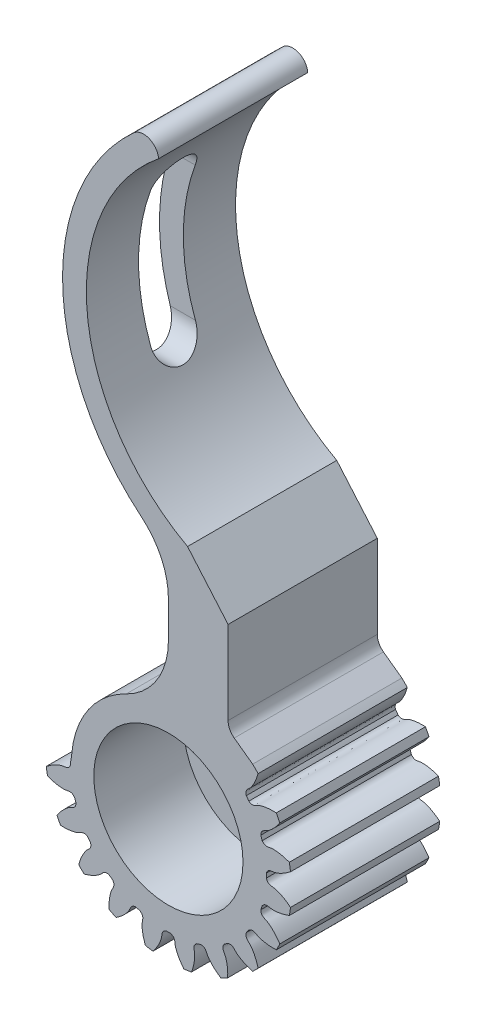
SolidWorks part; units mm, degrees
material "聚脂树脂"
ref_plane "前视基准面" through (0, 0, 0) normal (0, 0, 1) x (1, 0, 0)
ref_plane "上视基准面" through (0, 0, 0) normal (0, 1, 0) x (1, 0, 0)
ref_plane "右视基准面" through (0, 0, 0) normal (1, 0, 0) x (0, 0, -1)
other "Configuration Table"
sketch "草图1" plane through (0, 0, 0) normal (0, 0, 1) x (1, 0, 0)
  circle A0 centre (0, 0) radius 16.5
extrude "凸台-拉伸1" add sketch "草图1" along normal blind 20
ref_axis "基准轴1" through (0, 0, -1.5) along (0, 0, 1)
sketch "草图2" plane through (0, 0, 0) normal (0, 0, 1) x (1, 0, 0)
  line L0 (0, 0) -> (0, 16.5) construction
  circle A0 centre (0, 0) radius 16.5 construction
  arc A1 (0.29, 13.1218) -> (-0.29, 13.1218) centre (0, 0) ccw
  arc A2 (4.7717, 18.7474) -> (-4.7717, 18.7474) centre (0, 0) ccw
  spline S0 degree 3 poles (0.29, 13.1218) (0.9168, 13.3402) (0.8356, 13.7807) (0.9193, 14.205) (0.9283, 14.2463) (0.9395, 14.293) (0.9529, 14.3448) (0.969, 14.4018) (0.9878, 14.4638) (1.0095, 14.5309) (1.0345, 14.6028) (1.0629, 14.6795) (1.0948, 14.7608) (1.1305, 14.8467) (1.1702, 14.9371) (1.2141, 15.0317) (1.2623, 15.1305) (1.315, 15.2334) (1.3725, 15.3401) (1.4349, 15.4506) (1.5023, 15.5646) (1.575, 15.6821) (1.653, 15.8029) (1.7366, 15.9267) (1.826, 16.0534) (1.9211, 16.1829) (2.0223, 16.3149) (2.1296, 16.4493) (2.2432, 16.5859) (2.3632, 16.7244) (2.4897, 16.8646) (2.6229, 17.0065) (2.7628, 17.1496) (2.9095, 17.2939) (3.0632, 17.4391) (3.224, 17.585) (3.3918, 17.7313) (3.567, 17.8779) (3.7493, 18.0245) (3.9391, 18.1709) (4.1363, 18.3167) (4.4122, 18.5125) (4.6259, 18.6545) (4.7717, 18.7474) knots 0 0 0 0 0.165916 0.170906 0.176664 0.183189 0.190482 0.198542 0.207371 0.216967 0.22733 0.238462 0.250361 0.263027 0.276462 0.290664 0.305634 0.321371 0.337876 0.355149 0.37319 0.391998 0.411574 0.431917 0.453028 0.474907 0.497554 0.520968 0.54515 0.570099 0.595817 0.622302 0.649554 0.677575 0.706363 0.735918 0.766242 0.797333 0.829191 0.861818 0.895212 0.929373 1 1 1 1
  spline S1 degree 3 poles (-0.29, 13.1218) (-0.9168, 13.3402) (-0.8356, 13.7807) (-0.9193, 14.205) (-0.9283, 14.2463) (-0.9395, 14.293) (-0.9529, 14.3448) (-0.969, 14.4018) (-0.9878, 14.4638) (-1.0095, 14.5309) (-1.0345, 14.6028) (-1.0629, 14.6795) (-1.0948, 14.7608) (-1.1305, 14.8467) (-1.1702, 14.9371) (-1.2141, 15.0317) (-1.2623, 15.1305) (-1.315, 15.2334) (-1.3725, 15.3401) (-1.4349, 15.4506) (-1.5023, 15.5646) (-1.575, 15.6821) (-1.653, 15.8029) (-1.7366, 15.9267) (-1.826, 16.0534) (-1.9211, 16.1829) (-2.0223, 16.3149) (-2.1296, 16.4493) (-2.2432, 16.5859) (-2.3632, 16.7244) (-2.4897, 16.8646) (-2.6229, 17.0065) (-2.7628, 17.1496) (-2.9095, 17.2939) (-3.0632, 17.4391) (-3.224, 17.585) (-3.3918, 17.7313) (-3.567, 17.8779) (-3.7493, 18.0245) (-3.9391, 18.1709) (-4.1363, 18.3167) (-4.4122, 18.5125) (-4.6259, 18.6545) (-4.7717, 18.7474) knots 0 0 0 0 0.165916 0.170906 0.176664 0.183189 0.190482 0.198542 0.207371 0.216967 0.22733 0.238462 0.250361 0.263027 0.276462 0.290664 0.305634 0.321371 0.337876 0.355149 0.37319 0.391998 0.411574 0.431917 0.453028 0.474907 0.497554 0.520968 0.54515 0.570099 0.595817 0.622302 0.649554 0.677575 0.706363 0.735918 0.766242 0.797333 0.829191 0.861818 0.895212 0.929373 1 1 1 1
extrude "切除-拉伸1" cut sketch "草图2" along normal through all
pattern_circular "阵列(圆周)1" count 20 over 360 about axis through (0, 0, -1.5) along (0, 0, 1) of "切除-拉伸1"
sketch "草图3" plane through (0, 0, 0) normal (0, 0, 1) x (1, 0, 0)
  circle A0 centre (0, 0) radius 15 construction
  dimension "Dn" = 30
sketch "草图4" plane through (0, 0, 0) normal (0, 0, -1) x (-1, 0, 0)
  line L0 (0, 0) -> (67.6919, 0) construction
  line L1 (0, 13.125) -> (0, 76.7697) construction
  line L2 (-15, 0) -> (-15, 67.6903) construction
  line L6 (-7.9502, 14.4584) -> (-11.294, 12.029)
  line L7 (-8, 0) -> (-8, 30.72)
  line L8 (0, 30.72) -> (0, 0)
  line L9 (1.261, 80) -> (1.32, 76)
  line L10 (-8, 0) -> (0, 0)
  circle A2 centre (-15, 55.76) radius 26 construction
  arc A4 (-8, 30.72) -> (1.32, 76) centre (-15, 55.76) ccw
  arc A6 (0.29, 13.1218) -> (-0.29, 13.1218) centre (0, 0) ccw construction
  arc A7 (-2.0665, 16.3701) -> (-3.0932, 16.2075) centre (0, 0) ccw construction
  arc A8 (-3.7791, 12.5692) -> (-4.3306, 12.39) centre (0, 0) ccw construction
  arc A9 (-7.024, 14.9303) -> (-7.9502, 14.4584) centre (0, 0) ccw construction
  arc A10 (0, 13.125) -> (-0.29, 13.1218) centre (0, 0) ccw
  arc A11 (-2.0665, 16.3701) -> (-3.0932, 16.2075) centre (0, 0) ccw
  arc A12 (-3.7791, 12.5692) -> (-4.3306, 12.39) centre (0, 0) ccw
  arc A13 (-7.024, 14.9303) -> (-7.9502, 14.4584) centre (0, 0) ccw
  arc A14 (-7.4782, 10.7862) -> (-7.9474, 10.4453) centre (0, 0) ccw construction
  arc A15 (-7.4782, 10.7862) -> (-7.9474, 10.4453) centre (0, 0) ccw
  circle A16 centre (0, 0) radius 12.5
  circle A17 centre (-15, 55.76) radius 29.189 construction
  arc A18 (0, 30.72) -> (1.261, 80) centre (-15, 55.76) ccw
  spline S2 degree 3 poles (3856.7688, 1071.746) (-40.9447, -7.0022) (0.397, 7.533) (-0.9224, 14.2207) (-0.9359, 14.2793) (-0.9529, 14.3448) (-0.969, 14.4018) (-0.9951, 14.4881) (-1.0357, 14.6084) (-1.0961, 14.7664) (-1.1716, 14.9426) (-1.2638, 15.1361) (-1.3741, 15.3456) (-1.5041, 15.5702) (-1.6549, 15.8084) (-1.7965, 16.0133) (-1.9211, 16.1829) (-22.6396, 43.218) (-204.8238, -56.137) (3987.8439, 293.2807) knots -2.601051 -2.601051 -2.601051 -2.601051 0.165916 0.170906 0.183189 0.190482 0.198542 0.207371 0.22733 0.250361 0.276462 0.305634 0.337876 0.37319 0.411574 0.453028 0.474907 0.497554 14.365332 14.365332 14.365332 14.365332 only from (-0.29, 13.1218) to (-2.0665, 16.3701) construction
  spline S3 degree 3 poles (-3999.1929, -172.5161) (41.1045, 5.9931) (-2.7054, 7.0416) (-3.5171, 13.8097) (-3.5224, 13.8696) (-3.5265, 13.9372) (-3.5289, 13.9963) (-3.5307, 14.0865) (-3.5293, 14.2134) (-3.5206, 14.3824) (-3.5033, 14.5733) (-3.4754, 14.7858) (-3.4352, 15.0192) (-3.381, 15.2729) (-3.3111, 15.5461) (-3.2398, 15.7847) (-3.1737, 15.9845) (8.1764, 48.0988) (212.1463, 9.9046) (-3883.2936, -953.385) knots -2.108482 -2.108482 -2.108482 -2.108482 0.658484 0.663474 0.675757 0.68305 0.691111 0.699939 0.719899 0.742929 0.76903 0.798202 0.830445 0.865758 0.904142 0.945597 0.967475 0.990122 14.8579 14.8579 14.8579 14.8579 only from (-3.7791, 12.5692) to (-3.0932, 16.2075) construction
  spline S4 degree 3 poles (3336.8174, 2211.0982) (-36.7769, -19.3121) (-1.9503, 7.287) (-5.2717, 13.2396) (-5.3027, 13.2912) (-5.3391, 13.3482) (-5.3719, 13.3975) (-5.4235, 13.4715) (-5.4992, 13.5733) (-5.6055, 13.705) (-5.7318, 13.8492) (-5.8792, 14.0047) (-6.0489, 14.1699) (-6.2419, 14.3433) (-6.459, 14.5233) (-6.6569, 14.6744) (-6.8279, 14.7972) (-34.8866, 34.1067) (-177.4517, -116.6835) (3702.0362, 1511.238) knots -2.601051 -2.601051 -2.601051 -2.601051 0.165916 0.170906 0.183189 0.190482 0.198542 0.207371 0.22733 0.250361 0.276462 0.305634 0.337876 0.37319 0.411574 0.453028 0.474907 0.497554 14.365332 14.365332 14.365332 14.365332 only from (-4.3306, 12.39) to (-7.024, 14.9303) construction
  spline S5 degree 3 poles (-0.29, 13.1218) (-0.9168, 13.3402) (-0.8356, 13.7807) (-0.9224, 14.2207) (-0.9359, 14.2793) (-0.9529, 14.3448) (-0.969, 14.4018) (-0.9951, 14.4881) (-1.0357, 14.6084) (-1.0961, 14.7664) (-1.1716, 14.9426) (-1.2638, 15.1361) (-1.3741, 15.3456) (-1.5041, 15.5702) (-1.6549, 15.8084) (-1.828, 16.0589) (-1.969, 16.2466) (-2.0515, 16.3512) (-2.0665, 16.3701) knots 0 0 0 0 0.165916 0.170906 0.183189 0.190482 0.198542 0.207371 0.22733 0.250361 0.276462 0.305634 0.337876 0.37319 0.411574 0.453028 0.497554 0.507432 0.507432 0.507432 0.507432
  spline S6 degree 3 poles (-3.7791, 12.5692) (-3.2504, 12.9706) (-3.4637, 13.3644) (-3.5171, 13.8097) (-3.5224, 13.8696) (-3.5265, 13.9372) (-3.5289, 13.9963) (-3.5307, 14.0865) (-3.5293, 14.2134) (-3.5206, 14.3824) (-3.5033, 14.5733) (-3.4754, 14.7858) (-3.4352, 15.0192) (-3.381, 15.2729) (-3.3111, 15.5461) (-3.224, 15.8378) (-3.1479, 16.0599) (-3.1017, 16.1848) (-3.0932, 16.2075) knots 0.492568 0.492568 0.492568 0.492568 0.658484 0.663474 0.675757 0.68305 0.691111 0.699939 0.719899 0.742929 0.76903 0.798202 0.830445 0.865758 0.904142 0.945597 0.990122 1 1 1 1
  spline S7 degree 3 poles (-4.3306, 12.39) (-4.9943, 12.404) (-5.0532, 12.848) (-5.2717, 13.2396) (-5.3027, 13.2912) (-5.3391, 13.3482) (-5.3719, 13.3975) (-5.4235, 13.4715) (-5.4992, 13.5733) (-5.6055, 13.705) (-5.7318, 13.8492) (-5.8792, 14.0047) (-6.0489, 14.1699) (-6.2419, 14.3433) (-6.459, 14.5233) (-6.701, 14.7081) (-6.8931, 14.843) (-7.0039, 14.9169) (-7.024, 14.9303) knots 0 0 0 0 0.165916 0.170906 0.183189 0.190482 0.198542 0.207371 0.22733 0.250361 0.276462 0.305634 0.337876 0.37319 0.411574 0.453028 0.497554 0.507432 0.507432 0.507432 0.507432
  spline S8 degree 3 poles (-3750.148, -1399.8911) (37.2407, 18.4018) (-4.7489, 5.861) (-7.6124, 12.047) (-7.636, 12.1023) (-7.6607, 12.1653) (-7.6812, 12.2208) (-7.7108, 12.3061) (-7.7487, 12.4272) (-7.7927, 12.5905) (-7.8352, 12.7775) (-7.8743, 12.9882) (-7.9082, 13.2226) (-7.9351, 13.4806) (-7.9531, 13.762) (-7.959, 14.011) (-7.9578, 14.2215) (-7.0871, 48.2713) (198.7024, 74.9766) (-3398.6195, -2106.7268) knots -2.108482 -2.108482 -2.108482 -2.108482 0.658484 0.663474 0.675757 0.68305 0.691111 0.699939 0.719899 0.742929 0.76903 0.798202 0.830445 0.865758 0.904142 0.945597 0.967475 0.990122 14.8579 14.8579 14.8579 14.8579 only from (-7.4782, 10.7862) to (-7.9502, 14.4584) construction
  spline S9 degree 3 poles (2490.235, 3134.0126) (-29.0091, -29.7316) (-4.1066, 6.3277) (-9.105, 10.9626) (-9.1503, 11.0021) (-9.2026, 11.0451) (-9.2491, 11.0817) (-9.321, 11.1362) (-9.4245, 11.2097) (-9.5662, 11.302) (-9.7309, 11.4002) (-9.9192, 11.5025) (-10.1316, 11.6072) (-10.3687, 11.7125) (-10.6308, 11.8165) (-10.8658, 11.8991) (-11.0663, 11.963) (-43.7187, 21.6569) (-132.7094, -165.8082) (3053.8474, 2581.2649) knots -2.601051 -2.601051 -2.601051 -2.601051 0.165916 0.170906 0.183189 0.190482 0.198542 0.207371 0.22733 0.250361 0.276462 0.305634 0.337876 0.37319 0.411574 0.453028 0.474907 0.497554 14.365332 14.365332 14.365332 14.365332 only from (-7.9474, 10.4453) to (-11.294, 12.029) construction
  spline S10 degree 3 poles (-7.4782, 10.7862) (-7.0995, 11.3313) (-7.424, 11.64) (-7.6124, 12.047) (-7.636, 12.1023) (-7.6607, 12.1653) (-7.6812, 12.2208) (-7.7108, 12.3061) (-7.7487, 12.4272) (-7.7927, 12.5905) (-7.8352, 12.7775) (-7.8743, 12.9882) (-7.9082, 13.2226) (-7.9351, 13.4806) (-7.9531, 13.762) (-7.9603, 14.0664) (-7.9566, 14.3011) (-7.9513, 14.4342) (-7.9502, 14.4584) knots 0.492568 0.492568 0.492568 0.492568 0.658484 0.663474 0.675757 0.68305 0.691111 0.699939 0.719899 0.742929 0.76903 0.798202 0.830445 0.865758 0.904142 0.945597 0.990122 1 1 1 1
  spline S11 degree 3 poles (-7.9474, 10.4453) (-8.5829, 10.2536) (-8.7761, 10.6576) (-9.105, 10.9626) (-9.1503, 11.0021) (-9.2026, 11.0451) (-9.2491, 11.0817) (-9.321, 11.1362) (-9.4245, 11.2097) (-9.5662, 11.302) (-9.7309, 11.4002) (-9.9192, 11.5025) (-10.1316, 11.6072) (-10.3687, 11.7125) (-10.6308, 11.8165) (-10.9181, 11.9175) (-11.1425, 11.9864) (-11.2707, 12.0225) (-11.294, 12.029) knots 0 0 0 0 0.165916 0.170906 0.183189 0.190482 0.198542 0.207371 0.22733 0.250361 0.276462 0.305634 0.337876 0.37319 0.411574 0.453028 0.497554 0.507432 0.507432 0.507432 0.507432
  dimension "D4" = 52
  dimension "D5" = 80
  dimension "D3" = 25
  dimension "D1" = 15
  dimension "D2" = 30.72
  dimension "D6" = 76
  dimension "D8" = 8
  dimension "D9" = 30.72
extrude "凸台-拉伸2" add sketch "草图4" against normal blind 20 contours S7 A12 S6 A11 S5 A10 L8 A18 L9 A4 L7 L6 A13 | S11 L7 L6 | L6 S11 A15 S10 region at (7.2884, 22.5711, 0) region at (9.051, 12.2758, 0)
fillet "圆角1" radius 10 1 edges at (0, 30.72, 10)
fillet "圆角2" radius 2 2 edges at (8, 14.4222, 10) (-1.261, 80, 10)
sketch "草图5" plane through (0, 0, 0) normal (0, 0, -1) x (-1, 0, 0)
  line L0 (0, 0) -> (47.9973, 0) construction
  line L1 (0, 0) -> (0, 54.3289) construction
sketch "草图7" plane through (0, 0, 20) normal (0, 0, 1) x (1, 0, 0)
  line L0 (0, 0) -> (42.9933, 0) construction
  line L1 (0, 0) -> (0, 51.6895) construction
  circle A0 centre (0, 0) radius 10
  dimension "D1" = 20
extrude "切除-拉伸2" cut sketch "草图7" against normal blind 12
sketch "草图8" plane through (0, 0, 8) normal (0, 0, 1) x (1, 0, 0)
  line L0 (0, 0) -> (25.4464, 0) construction
  line L1 (0, 0) -> (0, 31.9913) construction
  circle A0 centre (0, 0) radius 3.5
  circle A1 centre (0, 7) radius 1.5
  circle A2 centre (7, 0) radius 1.5
  circle A3 centre (0, -7) radius 1.5
  circle A4 centre (-7, 0) radius 1.5
  dimension "D1" = 3
  dimension "D2" = 7
  dimension "D4" = 3
  dimension "D3" = 7
  dimension "D5" = 7
extrude "切除-拉伸3" cut sketch "草图8" against normal blind 10
chamfer "倒角1" distance 5 angle 45 1 edges at (8, 30.72, 10) first distance on face at (8, 23.0806, 10)
sketch "草图10" plane through (0, 0, 0) normal (0, 0, -1) x (-1, 0, 0)
  circle A0 centre (0, 0) radius 10
  circle A1 centre (-7, 0) radius 1.5 construction
  circle A2 centre (0, -7) radius 1.5 construction
  circle A3 centre (0, 0) radius 3.5 construction
  circle A4 centre (7, 0) radius 1.5 construction
  circle A5 centre (0, 7) radius 1.5 construction
  circle A6 centre (-7, 0) radius 1.5
  circle A7 centre (0, -7) radius 1.5
  circle A8 centre (0, 0) radius 3.5
  circle A9 centre (7, 0) radius 1.5
  circle A10 centre (0, 7) radius 1.5
  dimension "D1" = 20
extrude "凸台-拉伸3" add sketch "草图10" along normal blind 2
fillet "圆角3" radius 2 1 edges at (10, 0, 0)
sketch "草图11" plane through (0, 0, 0) normal (1, 0, 0) x (0, 0, -1)
  line L0 (-10, 46.72) -> (-10, 64.72) construction
  line L1 (-13, 46.72) -> (-13, 64.72)
  line L2 (-7, 46.72) -> (-7, 64.72)
  line L3 (0, 32.9259) -> (0, 76) construction
  arc A0 (-13, 46.72) -> (-7, 46.72) centre (-10, 46.72) ccw
  arc A1 (-7, 64.72) -> (-13, 64.72) centre (-10, 64.72) ccw
  point P2 (-10, 55.72)
  dimension "D2" = 3
  dimension "D1" = 18
  dimension "D3" = 10
  dimension "D4" = 55.72
extrude "切除-拉伸4" cut sketch "草图11" against normal blind 24
sketch "草图12" plane through (0, 0, -2) normal (0, 0, -1) x (-1, 0, 0)
  line L0 (0, 0) -> (0, 21.2383)
  line L1 (0, 25.5808) -> (0, 13.125) construction
  line L2 (0, 21.2383) -> (26.7629, 21.2383)
  line L3 (26.7629, 21.2383) -> (26.7629, 0)
  line L4 (26.7629, 0) -> (0, 0)
  circle A0 centre (0, 0) radius 13
  dimension "D1" = 26
extrude "切除-拉伸5" cut sketch "草图12" against normal blind 30 contours A0 L4 L3 L2 L0 region at (-15.7774, 12.1735, -2)
fillet "圆角4" radius 10 1 edges at (-13, 0, 10)
fillet "圆角5" radius 10 1 edges at (0, 13, 10)
